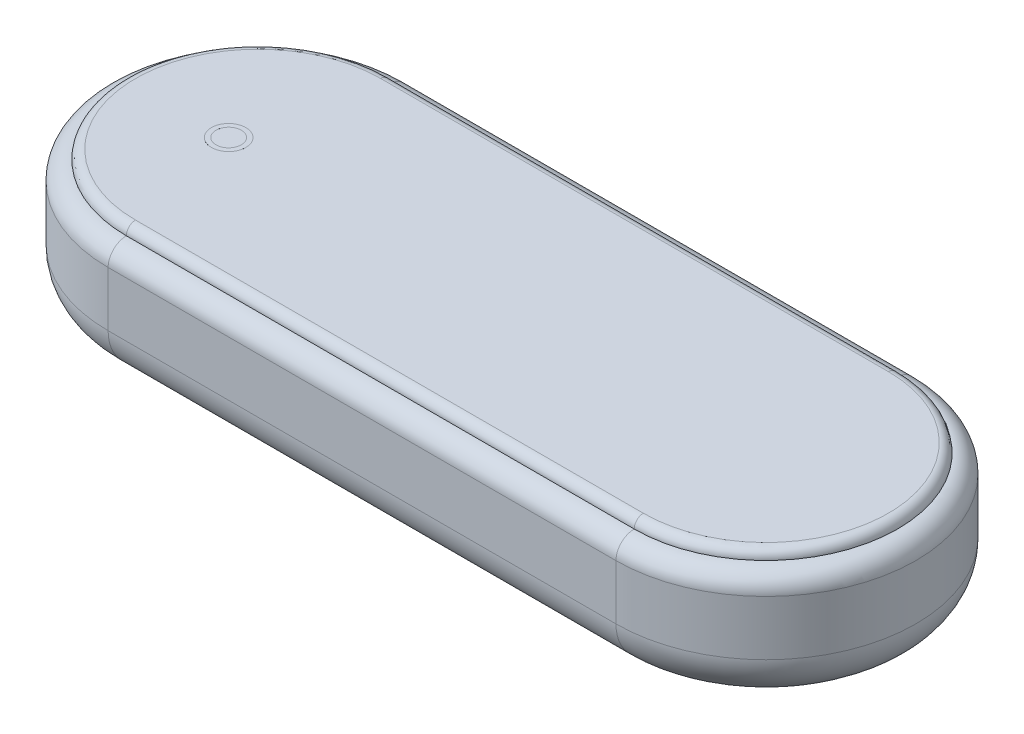
SolidWorks part; units mm, degrees
ref_plane "Front Plane" through (0, 0, 0) normal (0, 0, 1) x (1, 0, 0)
ref_plane "Top Plane" through (0, 0, 0) normal (0, 1, 0) x (1, 0, 0)
ref_plane "Right Plane" through (0, 0, 0) normal (1, 0, 0) x (0, 0, -1)
sketch "Sketch1" plane through (0, 0, 0) normal (0, 1, 0) x (1, 0, 0)
  line L0 (0, 0) -> (-55.6279, 0) construction
  line L1 (0, -16.4266) -> (-55.6279, -16.4266)
  line L2 (0, 16.4266) -> (-55.6279, 16.4266)
  arc A0 (0, -16.4266) -> (0, 16.4266) centre (0, 0) ccw
  arc A1 (-55.6279, 16.4266) -> (-55.6279, -16.4266) centre (-55.6279, 0) ccw
  point P3 (-27.8139, 0)
extrude "Boss-Extrude1" add sketch "Sketch1" along normal blind 13
fillet "Fillet1" radius 2 4 edges at (-72.0544, 13, 0) (-27.8139, 13, -16.4266) (16.4266, 13, 0) (-27.8139, 13, 16.4266)
sketch "Sketch2" plane through (0, 13, 0) normal (0, 1, 0) x (1, 0, 0)
  line L4 (0, 14.4266) -> (-55.6279, 14.4266)
  line L5 (-55.6279, -14.4266) -> (0, -14.4266)
  line L6 (0, 14.4266) -> (-55.6279, 14.4266)
  line L7 (-55.6279, -14.4266) -> (0, -14.4266)
  arc A4 (-55.6279, 14.4266) -> (-55.6279, -14.4266) centre (-55.6279, 0) ccw
  arc A5 (0, -14.4266) -> (0, 14.4266) centre (0, 0) ccw
  arc A6 (-55.6279, 14.4266) -> (-55.6279, -14.4266) centre (-55.6279, 0) ccw
  arc A7 (0, -14.4266) -> (0, 14.4266) centre (0, 0) ccw
  dimension "D1" = 0
extrude "Boss-Extrude2" add sketch "Sketch2" along normal blind 1 contours L6 A6 L7 A7
fillet "Fillet2" radius 1 4 edges at (-70.0544, 14, 0) (-27.8139, 14, -14.4266) (14.4266, 14, 0) (-27.8139, 14, 14.4266)
fillet "Fillet3" radius 5 4 edges at (-72.0544, 0, 0) (-27.8139, 0, -16.4266) (16.4266, 0, 0) (-27.8139, 0, 16.4266)
sketch "Sketch3" plane through (0, 0, 0) normal (0, -1, 0) x (1, 0, 0)
  line L0 (-67.0544, 0) -> (11.4266, 0) construction
  line L1 (-27.8139, 11.4266) -> (-27.8139, -11.4266) construction
  line L2 (0, 11.4266) -> (-55.6279, 11.4266) construction
  line L3 (-55.6279, -11.4266) -> (0, -11.4266) construction
  line L4 (-31.2703, 0) -> (-22.846, 0) construction
  line L5 (-31.2703, 4.4454) -> (-22.846, 4.4454)
  line L6 (-31.2703, -4.4454) -> (-22.846, -4.4454)
  arc A0 (-55.6279, 11.4266) -> (-55.6279, -11.4266) centre (-55.6279, 0) ccw construction
  arc A1 (0, -11.4266) -> (0, 11.4266) centre (0, 0) ccw construction
  arc A2 (-31.2703, 4.4454) -> (-31.2703, -4.4454) centre (-31.2703, 0) ccw
  arc A3 (-22.846, -4.4454) -> (-22.846, 4.4454) centre (-22.846, 0) ccw
  point P16 (-27.0582, 0)
extrude "Boss-Extrude3" add sketch "Sketch3" along normal blind 1
fillet "Fillet4" radius 0.5 4 edges at (-18.4006, 0, 0) (-27.0582, 0, -4.4454) (-35.7157, 0, 0) (-27.0582, 0, 4.4454)
sketch "Sketch4" plane through (0, -1, 0) normal (0, -1, 0) x (1, 0, 0)
  line L3 (-22.259, 0.639) -> (-23.433, 0.639)
  line L4 (-31.2703, -3.4454) -> (-22.846, -3.4454)
  line L5 (-22.846, 3.4454) -> (-31.2703, 3.4454)
  line L6 (-31.2703, -3.4454) -> (-22.846, -3.4454)
  line L7 (-22.846, 3.4454) -> (-31.2703, 3.4454)
  line L8 (-22.259, 0.639) -> (-22.259, -0.639)
  line L9 (-22.259, -0.639) -> (-23.433, -0.639)
  line L10 (-23.433, 0.639) -> (-23.433, -0.639)
  line L11 (-22.259, 0.639) -> (-23.433, -0.639) construction
  line L12 (-22.259, -0.639) -> (-23.433, 0.639) construction
  line L15 (-30.7136, 0.639) -> (-31.8271, 0.639)
  line L16 (-30.7136, 0.639) -> (-30.7136, -0.639)
  line L17 (-30.7136, -0.639) -> (-31.8271, -0.639)
  line L18 (-31.8271, 0.639) -> (-31.8271, -0.639)
  line L19 (-30.7136, 0.639) -> (-31.8271, -0.639) construction
  line L20 (-30.7136, -0.639) -> (-31.8271, 0.639) construction
  arc A4 (-31.2703, 3.4454) -> (-31.2703, -3.4454) centre (-31.2703, 0) ccw
  arc A5 (-22.846, -3.4454) -> (-22.846, 3.4454) centre (-22.846, 0) ccw
  arc A6 (-31.2703, 3.4454) -> (-31.2703, -3.4454) centre (-31.2703, 0) ccw
  arc A7 (-22.846, -3.4454) -> (-22.846, 3.4454) centre (-22.846, 0) ccw
  dimension "D1" = 1
extrude "Boss-Extrude4" add sketch "Sketch4" along normal blind 0.1
fillet "Fillet5" radius 0.5 4 edges at (-19.4006, -1.1, 0) (-27.0582, -1.1, -3.4454) (-34.7157, -1.1, 0) (-27.0582, -1.1, 3.4454)
fillet "Fillet6" radius 0.5 4 edges at (-18.4006, -1, 0) (-27.0582, -1, -4.4454) (-35.7157, -1, 0) (-27.0582, -1, 4.4454)
sketch "Sketch5" plane through (0, -1.1, 0) normal (0, -1, 0) x (1, 0, 0)
  line L0 (-27.0582, 3.1454) -> (-27.0582, -3.1454) construction
  line L1 (-22.846, 3.1454) -> (-31.2703, 3.1454) construction
  line L2 (-31.2703, -3.1454) -> (-22.846, -3.1454) construction
  line L3 (-19.7006, 0) -> (-34.4157, 0) construction
  line L5 (-25.888, 1.3148) -> (-28.2284, 1.3148)
  line L6 (-25.888, 1.3148) -> (-25.888, -1.3148)
  line L7 (-25.888, -1.3148) -> (-28.2284, -1.3148)
  line L8 (-28.2284, 1.3148) -> (-28.2284, -1.3148)
  line L9 (-25.888, 1.3148) -> (-28.2284, -1.3148) construction
  line L10 (-25.888, -1.3148) -> (-28.2284, 1.3148) construction
  arc A0 (-22.846, -3.1454) -> (-22.846, 3.1454) centre (-22.846, 0) ccw construction
  arc A1 (-31.2703, 3.1454) -> (-31.2703, -3.1454) centre (-31.2703, 0) ccw construction
  point P14 (-27.0582, 0)
extrude "Boss-Extrude5" add sketch "Sketch5" against normal blind 0.2
sketch "Sketch6" plane through (0, -1.1, 0) normal (0, -1, 0) x (1, 0, 0)
  line L0 (-19.7006, 0) -> (-34.4157, 0) construction
  line L1 (-27.0582, -3.1454) -> (-27.0582, 3.1454) construction
  line L2 (-31.2703, -3.1454) -> (-22.846, -3.1454) construction
  line L3 (-22.846, 3.1454) -> (-31.2703, 3.1454) construction
  line L5 (-26.041, -1.1075) -> (-28.0753, -1.1075)
  line L6 (-26.041, -1.1075) -> (-26.041, 1.1075)
  line L7 (-26.041, 1.1075) -> (-28.0753, 1.1075)
  line L8 (-28.0753, -1.1075) -> (-28.0753, 1.1075)
  line L9 (-26.041, -1.1075) -> (-28.0753, 1.1075) construction
  line L10 (-26.041, 1.1075) -> (-28.0753, -1.1075) construction
  arc A0 (-22.846, -3.1454) -> (-22.846, 3.1454) centre (-22.846, 0) ccw construction
  arc A1 (-31.2703, 3.1454) -> (-31.2703, -3.1454) centre (-31.2703, 0) ccw construction
  point P14 (-27.0582, 0)
extrude "Cut-Extrude1" cut sketch "Sketch6" against normal blind 0.1
sketch "Sketch7" plane through (0, 0, 0) normal (0, -1, 0) x (1, 0, 0)
  line L0 (-55.6279, 11.4266) -> (-55.6279, -11.4266) construction
  line L1 (-53.5645, 11.4266) -> (-53.5645, -11.4266) construction
  line L2 (0, 11.4266) -> (-55.6279, 11.4266) construction
  line L3 (-55.6279, -11.4266) -> (0, -11.4266) construction
  line L4 (-53.5645, 0) -> (-55.6279, 0) construction
  line L5 (-54.5962, 3.309) -> (-54.5962, -3.189) construction
  line L6 (-54.5962, 1.2482) -> (-54.5962, -1.2545) construction
  line L7 (-53.5645, 1.2482) -> (-53.5645, -1.2545)
  line L8 (-55.6279, 1.2482) -> (-55.6279, -1.2545)
  arc A0 (-55.6279, 11.4266) -> (-55.6279, -11.4266) centre (-55.6279, 0) ccw construction
  arc A1 (-53.5645, 1.2482) -> (-55.6279, 1.2482) centre (-54.5962, 1.2482) ccw
  arc A2 (-55.6279, -1.2545) -> (-53.5645, -1.2545) centre (-54.5962, -1.2545) ccw
  point P19 (-54.5962, -0.0032)
extrude "Cut-Extrude2" cut sketch "Sketch7" against normal blind 0.1
fillet "Fillet7" radius 0.5 4 edges at (-55.6279, 0.1, -0.0032) (-53.5645, 0.1, -0.0032) (-54.5962, 0.1, -2.2862) (-54.5962, 0.1, 2.2799)
sketch "Sketch9" plane through (0, 0.1, 0) normal (0, -1, 0) x (1, 0, 0)
  line L0 (-54.5962, 1.9799) -> (-54.5962, -1.9862) construction
  line L1 (-53.8645, 1.2482) -> (-55.3279, 1.2482) construction
  line L2 (-53.8645, -1.2545) -> (-55.3279, -1.2545) construction
  arc A0 (-53.8645, 1.2482) -> (-55.3279, 1.2482) centre (-54.5962, 1.2482) ccw construction
  arc A1 (-55.3279, -1.2545) -> (-53.8645, -1.2545) centre (-54.5962, -1.2545) ccw construction
  circle A2 centre (-54.5962, 1.2482) radius 0.5046
  circle A3 centre (-54.5811, -1.2522) radius 0.5046
extrude "Boss-Extrude6" add sketch "Sketch9" along normal blind 0.1
ref_plane "Plane1" through (0, 11.5, 0) normal (0, 1, 0) x (1, 0, 0)
sketch "Sketch14" plane through (0, 14, 0) normal (0, 1, 0) x (1, 0, 0)
  circle A2 centre (-58.3518, -0.5) radius 1.3869
  circle A3 centre (-58.3518, -0.5) radius 1.8869
  dimension "D1" = 0.5
extrude "Boss-Extrude7" add sketch "Sketch14" along normal blind 0.001
